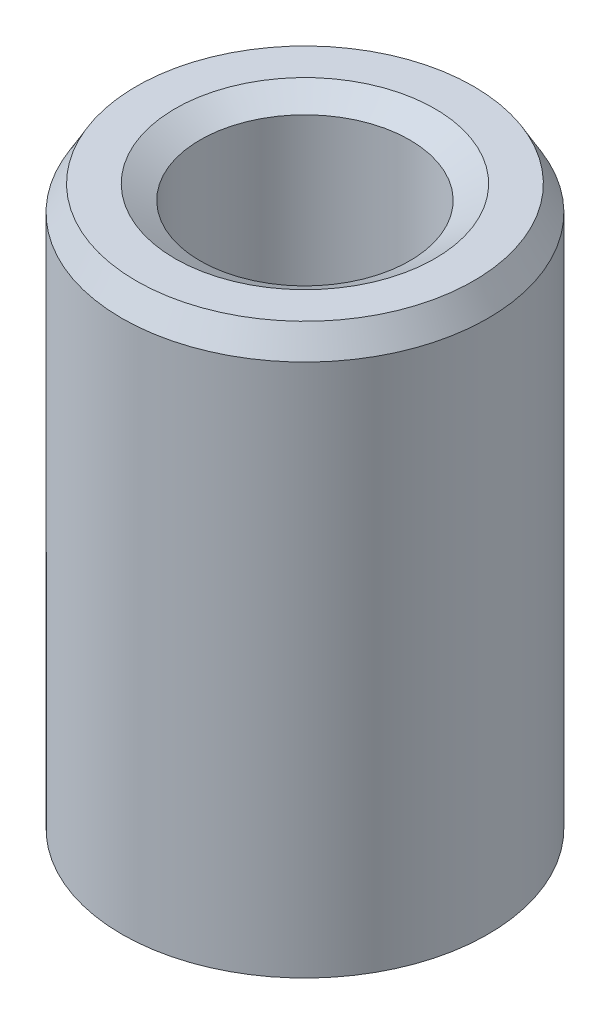
SolidWorks part; units mm, degrees
ref_plane "Front Plane" through (0, 0, 0) normal (0, 0, 1) x (1, 0, 0)
ref_plane "Top Plane" through (0, 0, 0) normal (0, 1, 0) x (1, 0, 0)
ref_plane "Right Plane" through (0, 0, 0) normal (1, 0, 0) x (0, 0, -1)
sketch "Sketch1" plane through (0, 0, 0) normal (0, 1, 0) x (1, 0, 0)
  circle A0 centre (0, 0) radius 10
  dimension "SLEEVE_OD" = 20
extrude "Boss-Extrude1" add sketch "Sketch1" along normal blind 31.2961
sketch "Sketch2" plane through (0, 0, 0) normal (0, 1, 0) x (1, 0, 0)
  circle A0 centre (0, 0) radius 5.7253
  dimension "BORE_D" = 11.4505
extrude "Cut-Extrude1" cut sketch "Sketch2" along normal through all
chamfer "Chamfer1" distance 1.3703 angle 30 4 edges at (0, 31.2961, 5.7253) (0, 0, 5.7253) (0, 0, 10) (0, 31.2961, 10) first distance on face at (0, 31.2961, 5.7253) first distance on face at (0, 0, 5.7253) first distance on face at (0, 31.2961, 10)
